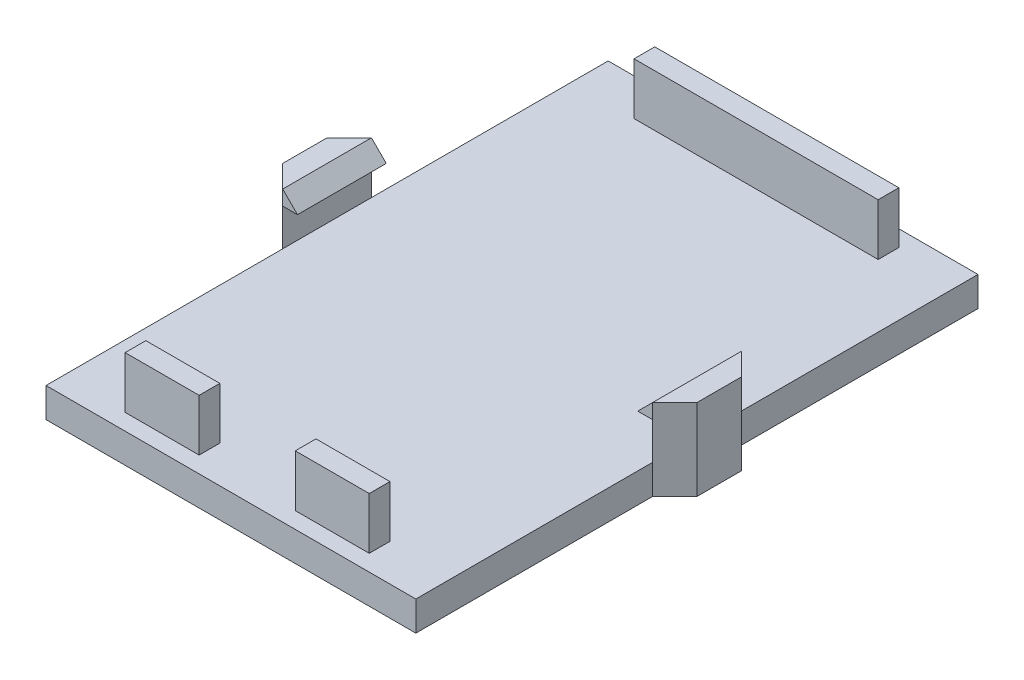
SolidWorks part; units mm, degrees
ref_plane "Front Plane" through (0, 0, 0) normal (0, 0, 1) x (1, 0, 0)
ref_plane "Top Plane" through (0, 0, 0) normal (0, 1, 0) x (1, 0, 0)
ref_plane "Right Plane" through (0, 0, 0) normal (1, 0, 0) x (0, 0, -1)
sketch "Sketch1" plane through (0, 0, 0) normal (0, 1, 0) x (1, 0, 0)
  line L0 (0, 0) -> (50000, 0) construction
  line L1 (-12.5, -19) -> (12.5, -19)
  line L2 (-12.5, -19) -> (-12.5, 19)
  line L3 (-12.5, 19) -> (12.5, 19)
  line L4 (12.5, -19) -> (12.5, 19)
  line L5 (-12.5, -19) -> (12.5, 19) construction
  line L6 (-12.5, 19) -> (12.5, -19) construction
  line L7 (0, 0) -> (0, 50000) construction
  line L8 (12.5, 3) -> (14, 1.5)
  line L9 (14, 1.5) -> (14, -1.5)
  line L10 (12.5, -3) -> (14, -1.5)
  line L11 (-12.5, -3) -> (-14, -1.5)
  line L12 (-14, 1.5) -> (-14, -1.5)
  line L13 (-12.5, 3) -> (-14, 1.5)
  line L14 (8.25, -16.5) -> (8.25, -17.9)
  line L15 (-8.25, 16.5) -> (8.25, 16.5)
  line L16 (-8.25, 16.5) -> (-8.25, 17.9)
  line L17 (-8.25, 17.9) -> (8.25, 17.9)
  line L18 (8.25, 16.5) -> (8.25, 17.9)
  line L19 (-8.25, 16.5) -> (8.25, 17.9) construction
  line L20 (-8.25, 17.9) -> (8.25, 16.5) construction
  line L21 (-8.25, -17.9) -> (8.25, -17.9)
  line L22 (-8.25, -16.5) -> (-8.25, -17.9)
  line L23 (-8.25, -16.5) -> (8.25, -16.5)
  point P0 (0, 0)
  point P15 (14, 0)
  point P20 (0, 17.2)
  dimension "D1" = 25
  dimension "D2" = 38
  dimension "D3" = 16
  dimension "D4" = 45
  dimension "D5" = 1.5
  dimension "D6" = 1.4
  dimension "D7" = 4.25
  dimension "D8" = 1.1
extrude "Boss-Extrude1" add sketch "Sketch1" along normal blind 2 contours L1 L4 L3 L2 region at (0, 0, 0)
extrude "Boss-Extrude2" add sketch "Sketch1<3>" along normal blind 5.5 contours L2 L13 L12 L11 | L4 L10 L9 L8 | L15 L18 L17 L16 | L23 L22 L21 L14 region at (-13.1667, 0, 0) region at (13.1667, 0, 0) region at (0, 0, 17.2) region at (0, 0, -17.2)
sketch "Sketch1<3>" plane through (0, 0, 0) normal (0, 1, 0) x (1, 0, 0) same geometry as "Sketch1"
sketch "Sketch2" plane through (0, 0, 0) normal (0, 0, 1) x (1, 0, 0)
  line L0 (12.5, 5.5) -> (11.5, 4.5)
  line L1 (11.5, 4.5) -> (12.5, 4.5)
  line L2 (12.5, 5.5) -> (12.5, 2) construction
  line L3 (12.5, 4.5) -> (12.5, 5.5)
  line L4 (0, -3.025) -> (0, 3.025) construction
  line L5 (-11.5, 4.5) -> (-12.5, 4.5)
  line L6 (-12.5, 4.5) -> (-12.5, 5.5)
  line L7 (-12.5, 5.5) -> (-11.5, 4.5)
  point P3 (11.7618, 4.7618)
  dimension "D1" = 1
extrude "Boss-Extrude3" add sketch "Sketch2" along normal up to vertex (3 mm away) and the other way up to vertex (3 mm away) up to point (12.5, 5.5, 3) other way up to point (12.5, 5.5, -3)
sketch "Sketch3" plane through (0, 2, 0) normal (0, 1, 0) x (1, 0, 0)
  line L0 (-8.25, -16.5) -> (8.25, -16.5) construction
  line L1 (-3.25, -17.9) -> (3.25, -17.9)
  line L2 (-3.25, -17.9) -> (-3.25, -16.5)
  line L3 (-3.25, -16.5) -> (3.25, -16.5)
  line L4 (3.25, -17.9) -> (3.25, -16.5)
  line L5 (-3.25, -17.9) -> (3.25, -16.5) construction
  line L6 (-3.25, -16.5) -> (3.25, -17.9) construction
  line L11 (-12.5, -19) -> (12.5, -19) construction
  line L13 (-8.25, -17.9) -> (8.25, -17.9) construction
  point P0 (0, -17.2)
  point P7 (0, 0)
  point P8 (-3.25, -17.615)
  point P12 (0, 0)
  point P17 (0, 0)
  point P18 (0, 0)
  point P21 (0, -19)
  dimension "D1" = 6.5
extrude "Cut-Extrude1" cut sketch "Sketch3" along normal up to surface (3.5 mm away) up to face at (0, 5.5, 17.2)
